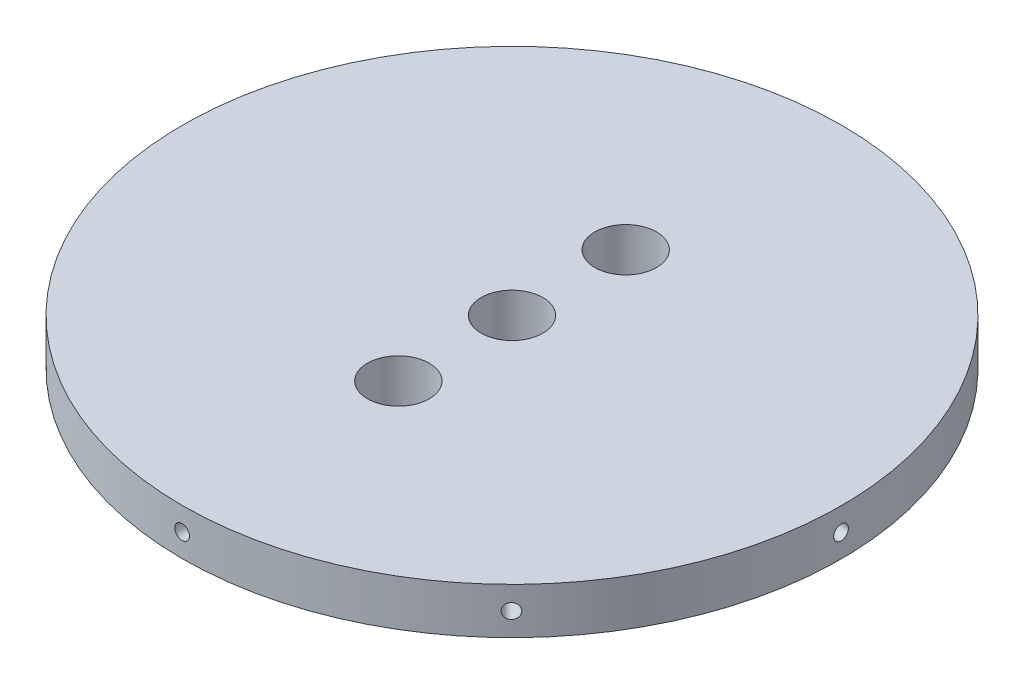
SolidWorks part; units mm, degrees
ref_plane "Front Plane" through (0, 0, 0) normal (0, 0, 1) x (1, 0, 0)
ref_plane "Top Plane" through (0, 0, 0) normal (0, 1, 0) x (1, 0, 0)
ref_plane "Right Plane" through (0, 0, 0) normal (1, 0, 0) x (0, 0, -1)
sketch "Sketch1" plane through (0, 0, 0) normal (0, 1, 0) x (1, 0, 0)
  circle A0 centre (0, 0) radius 50.8
  dimension "D1" = 101.6
extrude "Boss-Extrude1" add sketch "Sketch1" along normal blind 7.112 contours A0
sketch "Sketch2" plane through (0, 0, 0) normal (0, -1, 0) x (1, 0, 0)
  line L0 (0, 0) -> (-50.8, 0) construction
  line L1 (0, -17.526) -> (0, 17.526) construction
  circle A0 centre (0, 0) radius 50.8 construction
  circle A1 centre (0, 17.526) radius 4.7625
  circle A2 centre (0, 0) radius 4.7625
  circle A3 centre (0, -17.526) radius 4.7625
  point P9 (0, 0)
  dimension "D1" = 9.525
  dimension "D3" = 9.525
  dimension "D4" = 9.525
  dimension "D2" = 35.052
extrude "Cut-Extrude1" cut sketch "Sketch2" against normal through all contours A2 | A3 | A1 region at (0, 0, 0) region at (0, 0, -17.526)
ref_plane "Plane1" through (0, 0, 50.8) normal (0, 0, 1) x (1, 0, 0)
hole_wizard "#4-40 Tapped Hole1" positions "3DSketch4" profile "Sketch8" tap size "#4-40" standard "ANSI Inch"
sketch3d "3DSketch4"
  point P0 (17.0245, 10.3666, 0)
  point P2 (17.0245, 10.3666, 0)
  point P4 (17.0245, 10.3666, 0)
  point P6 (17.0245, 10.3666, 0)
  point P8 (17.0245, 10.3666, 0)
  point P10 (17.0245, 10.3666, 0)
  point P12 (17.0245, 10.3666, 0)
  point P14 (17.0245, 10.3666, 0)
  point P16 (17.0245, 10.3666, 0)
  point P18 (-0.0622, 3.5544, 50.8)
sketch "Sketch8" plane through (-0.0622, 3.5544, 50.8) normal (0, 1, 0) x (1, 0, 0.0012)
  line L0 (0, 0) -> (0, 10.2042)
  line L1 (0, 10.2042) -> (1.1303, 9.525)
  line L2 (1.1303, 9.525) -> (1.1303, 0)
  line L3 (50.8, 50.8) -> (-50.8, 50.8) construction
  line L5 (1.1303, 0) -> (0, 0)
  line L10 (0, 10.2042) -> (-1.1303, 9.525) construction
  line L11 (0, 0) -> (0, 101.6) construction
  circle A0 centre (0, 50.8) radius 50.8 construction
  dimension "Tap Drill Dia." = 2.2606
  dimension "Tap Drill Depth" = 9.525
  dimension "Drill Angle" = 118
cosmetic thread "Hole Thread1" parameters "D1"=9.525, "D2"=2.8448
pattern_circular "CirPattern7" count 8 over 360 about axis through (0, 7.112, 0) along (0, 1, 0) of "#4-40 Tapped Hole1"
cosmetic thread "Hole Thread2" parameters "D1"=9.525, "D2"=2.8448
cosmetic thread "Hole Thread3" parameters "D1"=9.525, "D2"=2.8448
cosmetic thread "Hole Thread4" parameters "D1"=9.525, "D2"=2.8448
cosmetic thread "Hole Thread5" parameters "D1"=9.525, "D2"=2.8448
cosmetic thread "Hole Thread6" parameters "D1"=9.525, "D2"=2.8448
cosmetic thread "Hole Thread7" parameters "D1"=9.525, "D2"=2.8448
cosmetic thread "Hole Thread8" parameters "D1"=9.525, "D2"=2.8448
equation "\"0..28in\"=0.1"
